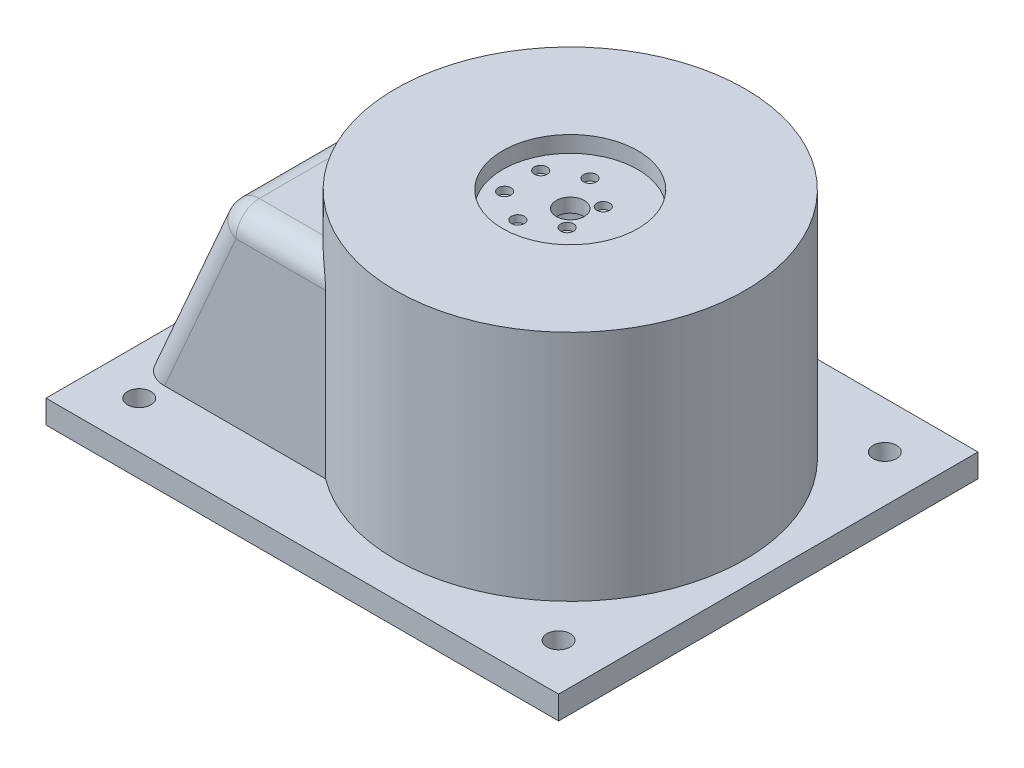
SolidWorks part; units mm, degrees
ref_plane "Front Plane" through (0, 0, 0) normal (0, 0, 1) x (1, 0, 0)
ref_plane "Top Plane" through (0, 0, 0) normal (0, 1, 0) x (1, 0, 0)
ref_plane "Right Plane" through (0, 0, 0) normal (1, 0, 0) x (0, 0, -1)
sketch "Sketch1" plane through (0, 0, 0) normal (0, 1, 0) x (1, 0, 0)
  circle A0 centre (0, 0) radius 75
  dimension "D1" = 150
extrude "Boss-Extrude1" add sketch "Sketch1" along normal blind 100
sketch "Sketch2" plane through (0, 0, 0) normal (0, 0, 1) x (1, 0, 0)
  line L0 (0, 100) -> (0, 0) construction
  line L1 (75, 100) -> (-75, 100) construction
  line L2 (0, 0) -> (-125, 0)
  line L3 (-125, 0) -> (-90, 80)
  line L4 (-90, 80) -> (0, 80)
  line L5 (0, 80) -> (0, 0)
  dimension "D1" = 125
  dimension "D2" = 90
  dimension "D3" = 80
sketch "Sketch5" plane through (0, 100, 0) normal (0, 1, 0) x (1, 0, 0)
  circle A0 centre (0, 0) radius 29
  dimension "D1" = 58
extrude "Cut-Extrude2" cut sketch "Sketch5" against normal blind 7
extrude "Boss-Extrude2" add sketch "Sketch2" along normal blind 60 and the other way blind 60
sketch "Sketch8" plane through (0, 0, 0) normal (0, -1, 0) x (1, 0, 0)
  line L0 (75, 0) -> (-125, 0) construction
  line L1 (-125, -60) -> (-125, 60) construction
  line L3 (-135, 90) -> (85, 90)
  line L4 (-135, 90) -> (-135, -90)
  line L5 (-135, -90) -> (85, -90)
  line L6 (85, 90) -> (85, -90)
  line L7 (-135, 90) -> (85, -90) construction
  line L8 (-135, -90) -> (85, 90) construction
  arc A0 (-45, -60) -> (-45, 60) centre (0, 0) ccw construction
  point P7 (-25, 0)
  dimension "D1" = 220
  dimension "D2" = 180
extrude "Boss-Extrude3" add sketch "Sketch8" along normal blind 10
sketch "Sketch9" plane through (0, -10, 0) normal (0, -1, 0) x (1, 0, 0)
  line L0 (-115, 70) -> (-115, 90) construction
  line L1 (85, 90) -> (-135, 90) construction
  line L2 (-115, 70) -> (-135, 70) construction
  line L3 (-135, 90) -> (-135, -90) construction
  line L4 (-25, 90) -> (-25, -90) construction
  line L5 (-135, -90) -> (85, -90) construction
  line L6 (-135, 0) -> (85, 0) construction
  line L7 (85, -90) -> (85, 90) construction
  circle A0 centre (-115, 70) radius 5
  circle A1 centre (65, 70) radius 5
  circle A2 centre (65, -70) radius 5
  circle A3 centre (-115, -70) radius 5
  dimension "D1" = 10
  dimension "D2" = 20
  dimension "D3" = 20
extrude "Cut-Extrude4" cut sketch "Sketch9" against normal blind 10
fillet "Fillet1" radius 10 5 edges at (-107.5, 40, 60) (-67.5, 80, 60) (-90, 80, 0) (-107.5, 40, -60) (-67.5, 80, -60)
sketch "Sketch14" plane through (0, 93, 0) normal (0, 1, 0) x (1, 0, 0)
  circle A0 centre (0, 0) radius 6
  dimension "D1" = 12
extrude "Cut-Extrude6" cut sketch "Sketch14" against normal blind 110
sketch "Sketch15" plane through (0, -10, 0) normal (0, -1, 0) x (1, 0, 0)
  line L0 (0, 0) -> (-7, 0) construction
  circle A1 centre (-7, 0) radius 18.5
  dimension "D1" = 7
  dimension "D2" = 37
extrude "Cut-Extrude7" cut sketch "Sketch15" against normal blind 97
sketch "Sketch16" plane through (0, 87, 0) normal (0, -1, 0) x (1, 0, 0)
  line L0 (-7, 18.5) -> (-7, -18.5) construction
  line L1 (-7, 0) -> (-7, 15.5) construction
  circle A0 centre (-7, 0) radius 18.5 construction
  circle A1 centre (-7, 15.5) radius 1.5
  circle A2 centre (6.4234, 7.75) radius 1.5
  circle A3 centre (6.4234, -7.75) radius 1.5
  circle A4 centre (-7, -15.5) radius 1.5
  circle A5 centre (-20.4234, -7.75) radius 1.5
  circle A6 centre (-20.4234, 7.75) radius 1.5
  point P21 (-7, 0)
  dimension "D2" = 3
  dimension "D1" = 15.5
  dimension "D3" = 6
extrude "Cut-Extrude8" cut sketch "Sketch16" against normal blind 7
sketch "Sketch17" plane through (0, -10, 0) normal (0, -1, 0) x (1, 0, 0)
  line L0 (0, 0) -> (-135, 0) construction
  line L1 (-135, 90) -> (-135, -90) construction
  circle A0 centre (0, 0) radius 55
  dimension "D1" = 110
extrude "Cut-Extrude9" cut sketch "Sketch17" against normal blind 73
sketch "Sketch21" plane through (0, -10, 0) normal (0, -1, 0) x (1, 0, 0)
  line L0 (0, 0) -> (-60, 0) construction
  line L2 (-60, 40) -> (0, 40)
  line L3 (-60, 40) -> (-60, -40)
  line L4 (-60, -40) -> (0, -40)
  line L5 (0, 40) -> (0, -40)
  line L6 (-60, 40) -> (0, -40) construction
  line L7 (-60, -40) -> (0, 40) construction
  point P4 (-30, 0)
  dimension "D1" = 60
  dimension "D2" = 80
extrude "Cut-Extrude10" cut sketch "Sketch21" against normal blind 73
sketch "Sketch23" plane through (0, 93, 0) normal (0, 1, 0) x (1, 0, 0)
  line L0 (-7, 17) -> (-7, -17) construction
  line L1 (-8.5, 15.5) -> (-5.5, 15.5) construction
  line L2 (-7, 0) -> (-17.0977, 0) construction
  circle A0 centre (-7, 15.5) radius 1.5 construction
  circle A1 centre (-7, -15.5) radius 1.5 construction
  circle A2 centre (-7, 15.5) radius 2.75
  circle A3 centre (6.4234, 7.75) radius 2.75
  circle A4 centre (6.4234, -7.75) radius 2.75
  circle A5 centre (-7, -15.5) radius 2.75
  circle A6 centre (-20.4234, -7.75) radius 2.75
  circle A7 centre (-20.4234, 7.75) radius 2.75
  point P27 (-7, 0)
  dimension "D1" = 5.5
  dimension "D2" = 6
extrude "Cut-Extrude11" cut sketch "Sketch23" against normal blind 3
sketch "Sketch27" plane through (0, 0, 0) normal (0, 0, 1) x (1, 0, 0)
  line L0 (-25, -10) -> (-25, 63)
  line L1 (85, -10) -> (-135, -10) construction
  line L2 (-25, 63) -> (-74.6136, 63)
  line L3 (-74.6136, 63) -> (-106.5511, -10)
  line L4 (-106.5511, -10) -> (-25, -10)
  line L5 (-83.4598, 70) -> (-114.0848, 0) construction
  line L6 (-45, 70) -> (-83.4598, 70) construction
  dimension "D1" = 73
extrude "Cut-Extrude15" cut sketch "Sketch27" against normal blind 40 and the other way blind 40
